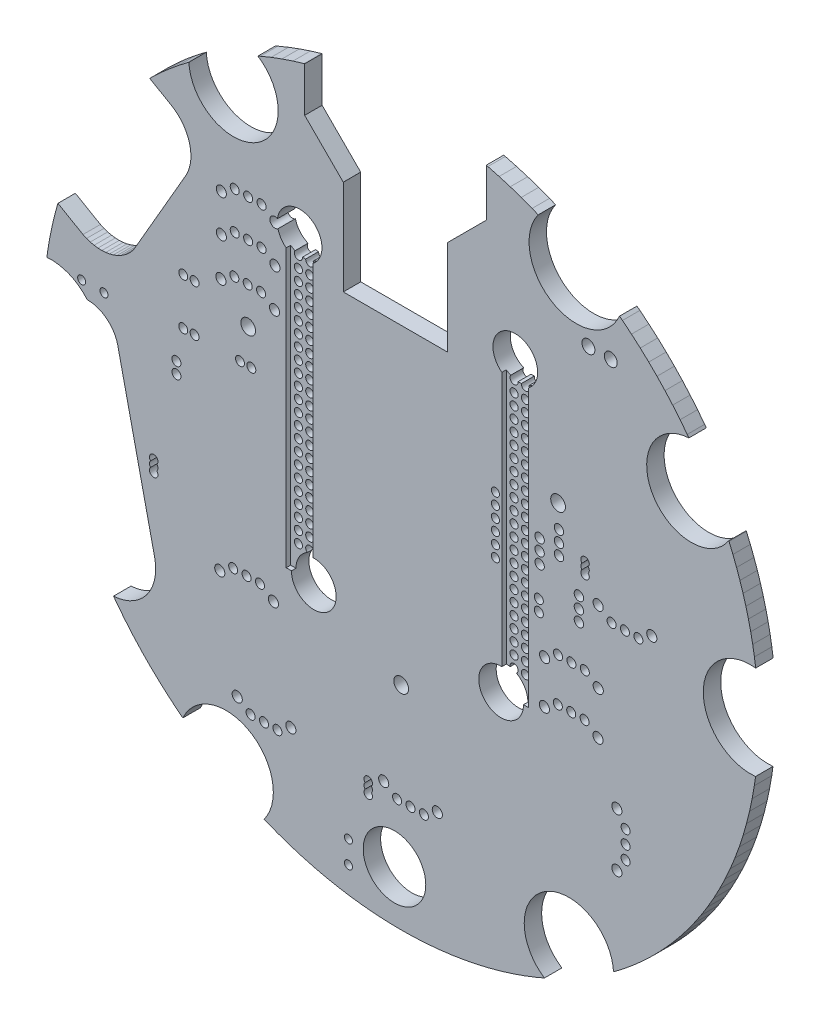
SolidWorks part; units mm, degrees
ref_plane "Płaszczyzna przednia" through (0, 0, 0) normal (0, 0, 1) x (1, 0, 0)
ref_plane "Płaszczyzna górna" through (0, 0, 0) normal (0, 1, 0) x (1, 0, 0)
ref_plane "Płaszczyzna prawa" through (0, 0, 0) normal (1, 0, 0) x (0, 0, -1)
sketch "Szkic1" plane through (0, 0, 0) normal (0, 0, 1) x (1, 0, 0)
  line L362 (-71.5796, -7.9834) -> (-71.3126, -9.14)
  line L363 (-71.3126, -9.14) -> (-68.5352, -8.4988)
  line L364 (-68.5352, -8.4988) -> (-68.1939, -8.42)
  line L365 (-68.1939, -8.42) -> (-67.4966, -8.3528)
  line L366 (-67.4966, -8.3528) -> (-66.7965, -8.3773)
  line L367 (-66.7965, -8.3773) -> (-66.1056, -8.4929)
  line L368 (-66.1056, -8.4929) -> (-65.4357, -8.6977)
  line L369 (-65.4357, -8.6977) -> (-64.7982, -8.9882)
  line L370 (-64.7982, -8.9882) -> (-64.2042, -9.3594)
  line L371 (-64.2042, -9.3594) -> (-63.6636, -9.805)
  line L372 (-63.6636, -9.805) -> (-63.1859, -10.3174)
  line L373 (-63.1859, -10.3174) -> (-62.7791, -10.8877)
  line L374 (-62.7791, -10.8877) -> (-62.4502, -11.5062)
  line L375 (-62.4502, -11.5062) -> (-62.2049, -12.1624)
  line L376 (-62.2049, -12.1624) -> (-62.1261, -12.5037)
  line L377 (-62.1261, -12.5037) -> (-61.3306, -15.949)
  line L378 (-61.3306, -15.949) -> (-61.2518, -16.2903)
  line L379 (-61.2518, -16.2903) -> (-61.1847, -16.9876)
  line L380 (-61.1847, -16.9876) -> (-61.2092, -17.6877)
  line L381 (-61.2092, -17.6877) -> (-61.3248, -18.3787)
  line L382 (-61.3248, -18.3787) -> (-61.5296, -19.0486)
  line L383 (-61.5296, -19.0486) -> (-61.8201, -19.686)
  line L384 (-61.8201, -19.686) -> (-62.1913, -20.2801)
  line L385 (-62.1913, -20.2801) -> (-62.6369, -20.8206)
  line L386 (-62.6369, -20.8206) -> (-63.1492, -21.2984)
  line L387 (-63.1492, -21.2984) -> (-63.7196, -21.7052)
  line L388 (-63.7196, -21.7052) -> (-64.3381, -22.0341)
  line L389 (-64.3381, -22.0341) -> (-64.9942, -22.2794)
  line L390 (-64.9942, -22.2794) -> (-65.3355, -22.3582)
  line L391 (-65.3355, -22.3582) -> (-76.0559, -24.8332)
  line L392 (-76.0559, -24.8332) -> (-75.5463, -26.3728)
  line L393 (-75.5463, -26.3728) -> (-74.6507, -28.8104)
  line L394 (-74.6507, -28.8104) -> (-73.6765, -31.2177)
  line L395 (-73.6765, -31.2177) -> (-73.3045, -32.0573)
  line L396 (-64.3703, -47.5137) -> (-63.5862, -48.5784)
  line L397 (-63.5862, -48.5784) -> (-61.8317, -50.7929)
  line L398 (-61.8317, -50.7929) -> (-60, -52.944)
  line L399 (-60, -52.944) -> (-58.0936, -55.0292)
  line L400 (-58.0936, -55.0292) -> (-56.1147, -57.0457)
  line L401 (-56.1147, -57.0457) -> (-54.0659, -58.9911)
  line L402 (-54.0659, -58.9911) -> (-51.9496, -60.863)
  line L403 (-51.9496, -60.863) -> (-49.7687, -62.659)
  line L404 (-49.7687, -62.659) -> (-48.854, -63.3595)
  line L405 (-30.6643, -73.9045) -> (-30.3309, -74.048)
  line L406 (-30.3309, -74.048) -> (-27.6979, -75.0726)
  line L407 (-27.6979, -75.0726) -> (-25.0304, -76.0036)
  line L408 (-25.0304, -76.0036) -> (-22.3317, -76.8399)
  line L409 (-22.3317, -76.8399) -> (-19.6051, -77.5804)
  line L410 (-19.6051, -77.5804) -> (-16.8541, -78.2241)
  line L411 (-16.8541, -78.2241) -> (-14.0821, -78.7703)
  line L412 (-14.0821, -78.7703) -> (-11.2926, -79.2184)
  line L413 (-11.2926, -79.2184) -> (-8.4889, -79.5676)
  line L414 (-8.4889, -79.5676) -> (-5.6747, -79.8177)
  line L415 (-5.6747, -79.8177) -> (-2.8534, -79.9683)
  line L416 (-2.8534, -79.9683) -> (-0.0286, -80.0192)
  line L417 (-0.0286, -80.0192) -> (2.7963, -79.9703)
  line L418 (2.7963, -79.9703) -> (5.6177, -79.8218)
  line L419 (5.6177, -79.8218) -> (8.4321, -79.5737)
  line L420 (8.4321, -79.5737) -> (11.236, -79.2264)
  line L421 (11.236, -79.2264) -> (14.0259, -78.7804)
  line L422 (14.0259, -78.7804) -> (16.7983, -78.2361)
  line L423 (16.7983, -78.2361) -> (19.5497, -77.5943)
  line L424 (19.5497, -77.5943) -> (22.2768, -76.8558)
  line L425 (22.2768, -76.8558) -> (24.9761, -76.0215)
  line L426 (24.9761, -76.0215) -> (27.6443, -75.0924)
  line L427 (27.6443, -75.0924) -> (30.278, -74.0697)
  line L428 (30.278, -74.0697) -> (32.0581, -73.3051)
  line L429 (47.514, -64.3751) -> (47.9923, -64.0295)
  line L430 (47.9923, -64.0295) -> (50.2037, -62.3107)
  line L431 (50.2037, -62.3107) -> (52.3536, -60.5156)
  line L432 (52.3536, -60.5156) -> (54.4394, -58.6463)
  line L433 (54.4394, -58.6463) -> (56.4584, -56.7052)
  line L434 (56.4584, -56.7052) -> (58.4083, -54.6947)
  line L435 (58.4083, -54.6947) -> (60.2867, -52.6171)
  line L436 (60.2867, -52.6171) -> (62.0911, -50.475)
  line L437 (62.0911, -50.475) -> (63.8195, -48.2711)
  line L438 (63.8195, -48.2711) -> (65.4698, -46.0081)
  line L439 (65.4698, -46.0081) -> (67.0398, -43.6887)
  line L440 (67.0398, -43.6887) -> (68.5277, -41.3158)
  line L441 (68.5277, -41.3158) -> (69.9316, -38.8923)
  line L442 (69.9316, -38.8923) -> (71.2498, -36.4211)
  line L443 (71.2498, -36.4211) -> (72.4808, -33.9053)
  line L444 (72.4808, -33.9053) -> (73.623, -31.348)
  line L445 (73.623, -31.348) -> (74.6749, -28.7523)
  line L446 (74.6749, -28.7523) -> (75.6354, -26.1213)
  line L447 (75.6354, -26.1213) -> (76.5032, -23.4583)
  line L448 (76.5032, -23.4583) -> (77.2773, -20.7666)
  line L449 (77.2773, -20.7666) -> (77.9567, -18.0495)
  line L450 (77.9567, -18.0495) -> (78.5407, -15.3102)
  line L451 (78.5407, -15.3102) -> (79.0284, -12.5522)
  line L452 (79.0284, -12.5522) -> (79.2994, -10.6289)
  line L453 (79.3336, 10.3964) -> (79.0449, 12.4201)
  line L454 (79.0449, 12.4201) -> (78.6613, 14.6547)
  line L455 (78.6613, 14.6547) -> (78.2145, 16.8775)
  line L456 (78.2145, 16.8775) -> (77.7049, 19.0868)
  line L457 (77.7049, 19.0868) -> (77.1329, 21.2808)
  line L458 (77.1329, 21.2808) -> (76.499, 23.4576)
  line L459 (76.499, 23.4576) -> (75.8037, 25.6157)
  line L460 (75.8037, 25.6157) -> (75.0475, 27.7531)
  line L461 (75.0475, 27.7531) -> (74.231, 29.8683)
  line L462 (74.231, 29.8683) -> (73.355, 31.9595)
  line L463 (73.355, 31.9595) -> (73.3082, 32.0629)
  line L464 (64.3736, 47.5139) -> (64.0078, 48.0184)
  line L465 (64.0078, 48.0184) -> (62.4143, 50.0722)
  line L466 (62.4143, 50.0722) -> (60.7549, 52.0732)
  line L467 (60.7549, 52.0732) -> (59.0313, 54.0192)
  line L468 (59.0313, 54.0192) -> (57.2455, 55.9082)
  line L469 (57.2455, 55.9082) -> (55.3992, 57.7382)
  line L470 (55.3992, 57.7382) -> (53.4945, 59.5072)
  line L471 (53.4945, 59.5072) -> (51.5333, 61.2135)
  line L472 (51.5333, 61.2135) -> (49.5177, 62.8551)
  line L473 (49.5177, 62.8551) -> (48.8544, 63.3604)
  line L474 (30.6602, 73.899) -> (29.2981, 74.4606)
  line L475 (29.2981, 74.4606) -> (26.864, 75.373)
  line L476 (26.864, 75.373) -> (24.4015, 76.2059)
  line L477 (24.4015, 76.2059) -> (21.9132, 76.9583)
  line L478 (21.9132, 76.9583) -> (19.4018, 77.6295)
  line L479 (19.4018, 77.6295) -> (19.0436, 77.7128)
  line L480 (19.0436, 77.7128) -> (19.0437, 67.0537)
  line L481 (19.0437, 67.0537) -> (10.4176, 58.4277)
  line L482 (10.4176, 58.4277) -> (10.4176, 37.1511)
  line L483 (10.4176, 37.1511) -> (-12.9504, 37.1511)
  line L484 (-12.9504, 37.1511) -> (-12.9504, 58.4177)
  line L485 (-12.9504, 58.4177) -> (-12.9604, 58.4177)
  line L486 (-12.9604, 58.4177) -> (-21.5964, 67.0537)
  line L487 (-21.5964, 67.0537) -> (-21.5964, 77.0457)
  line L488 (-21.5964, 77.0457) -> (-21.7211, 77.0127)
  line L489 (-21.7211, 77.0127) -> (-24.2112, 76.2665)
  line L490 (-24.2112, 76.2665) -> (-26.6758, 75.4398)
  line L491 (-26.6758, 75.4398) -> (-29.1122, 74.5335)
  line L492 (-29.1122, 74.5335) -> (-31.5179, 73.5485)
  line L493 (-31.5179, 73.5485) -> (-32.0595, 73.306)
  line L494 (-47.5141, 64.3762) -> (-47.8425, 64.1394)
  line L495 (-47.8425, 64.1394) -> (-49.8986, 62.5531)
  line L496 (-49.8986, 62.5531) -> (-51.9022, 60.9009)
  line L497 (-51.9022, 60.9009) -> (-53.8511, 59.1846)
  line L498 (-53.8511, 59.1846) -> (-55.7433, 57.406)
  line L499 (-55.7433, 57.406) -> (-56.2765, 56.8712)
  line L500 (-56.2765, 56.8712) -> (-51.5136, 54.1214)
  line L501 (-51.5136, 54.1214) -> (-51.1354, 53.903)
  line L502 (-51.1354, 53.903) -> (-50.4254, 53.3942)
  line L503 (-50.4254, 53.3942) -> (-49.7687, 52.8183)
  line L504 (-49.7687, 52.8183) -> (-49.1716, 52.1808)
  line L505 (-49.1716, 52.1808) -> (-48.6398, 51.4878)
  line L506 (-48.6398, 51.4878) -> (-48.1786, 50.746)
  line L507 (-48.1786, 50.746) -> (-47.7923, 49.9626)
  line L508 (-47.7923, 49.9626) -> (-47.4846, 49.1452)
  line L509 (-47.4846, 49.1452) -> (-47.2585, 48.3014)
  line L510 (-47.2585, 48.3014) -> (-47.1162, 47.4396)
  line L511 (-47.1162, 47.4396) -> (-47.0591, 46.568)
  line L512 (-47.0591, 46.568) -> (-47.0877, 45.695)
  line L513 (-47.0877, 45.695) -> (-47.2017, 44.829)
  line L514 (-47.2017, 44.829) -> (-47.4, 43.9784)
  line L515 (-47.4, 43.9784) -> (-47.6808, 43.1512)
  line L516 (-47.6808, 43.1512) -> (-48.0413, 42.3556)
  line L517 (-48.0413, 42.3556) -> (-48.2597, 41.9774)
  line L518 (-48.2597, 41.9774) -> (-59.4357, 22.62)
  line L519 (-59.4357, 22.62) -> (-59.654, 22.2418)
  line L520 (-59.654, 22.2418) -> (-60.1628, 21.5318)
  line L521 (-60.1628, 21.5318) -> (-60.7387, 20.8751)
  line L522 (-60.7387, 20.8751) -> (-61.3762, 20.278)
  line L523 (-61.3762, 20.278) -> (-62.0692, 19.7462)
  line L524 (-62.0692, 19.7462) -> (-62.811, 19.285)
  line L525 (-62.811, 19.285) -> (-63.5944, 18.8986)
  line L526 (-63.5944, 18.8986) -> (-64.4119, 18.591)
  line L527 (-64.4119, 18.591) -> (-65.2556, 18.3649)
  line L528 (-65.2556, 18.3649) -> (-66.1174, 18.2226)
  line L529 (-66.1174, 18.2226) -> (-66.989, 18.1655)
  line L530 (-66.989, 18.1655) -> (-67.862, 18.1941)
  line L531 (-67.862, 18.1941) -> (-68.728, 18.3081)
  line L532 (-68.728, 18.3081) -> (-69.5787, 18.5064)
  line L533 (-69.5787, 18.5064) -> (-70.4058, 18.7872)
  line L534 (-70.4058, 18.7872) -> (-71.2014, 19.1477)
  line L535 (-71.2014, 19.1477) -> (-71.5796, 19.366)
  line L536 (-71.5796, 19.366) -> (-76.8174, 22.3901)
  line L537 (-76.8174, 22.3901) -> (-76.8834, 22.1744)
  line L538 (-76.8834, 22.1744) -> (-77.5625, 19.6678)
  line L539 (-77.5625, 19.6678) -> (-78.1599, 17.1405)
  line L540 (-78.1599, 17.1405) -> (-78.6749, 14.5952)
  line L541 (-78.6749, 14.5952) -> (-79.1071, 12.0345)
  line L542 (-79.1071, 12.0345) -> (-79.2897, 10.6872)
  circle A3 centre (0, -32.54) radius 3
  circle A4 centre (35.1087, 20.27) radius 3
  circle A5 centre (-34.2427, 19.77) radius 3
  arc A16 (-71.5796, -7.9834) -> (-79.2897, 10.6872) centre (-78.3301, 0.1563) ccw
  arc A17 (-64.3703, -47.5137) -> (-73.3045, -32.0573) centre (-64.9348, -37.5297) ccw
  arc A18 (-30.6643, -73.9045) -> (-48.854, -63.3595) centre (-39.186, -67.6433) ccw
  arc A19 (47.514, -64.3751) -> (32.0581, -73.3051) centre (37.5297, -64.9348) ccw
  arc A20 (79.3336, 10.3964) -> (79.2994, -10.6289) centre (78.1738, -0.1144) ccw
  arc A21 (64.3736, 47.5139) -> (73.3082, 32.0629) centre (64.9348, 37.5297) ccw
  arc A22 (30.6602, 73.899) -> (48.8544, 63.3604) centre (39.186, 67.6433) ccw
  arc A23 (-47.5141, 64.3762) -> (-32.0595, 73.306) centre (-37.5297, 64.9348) ccw
extrude "Dodanie-wyciągnięcie1" add sketch "Szkic1" along normal blind 3.9
sketch "Sketch1" plane through (0, 0, 3.9) normal (0, 0, 1) x (1, 0, 0)
  line L6 (22.531, 39.311) -> (22.531, -17.7321)
  line L7 (28.531, 39.311) -> (28.531, -22.689)
  line L8 (28.531, -22.689) -> (27.3558, -22.689)
  line L9 (-19.729, 39.311) -> (-19.729, -17.7321)
  line L10 (-25.729, 39.311) -> (-25.729, -22.689)
  line L11 (-25.729, -22.689) -> (-24.5539, -22.6966)
  arc A4 (22.531, -17.7321) -> (27.3558, -22.689) centre (22.356, -22.729) ccw
  arc A5 (-24.5539, -22.6966) -> (-19.729, -17.7321) centre (-19.554, -22.729) ccw
  arc A6 (28.531, 39.311) -> (22.531, 39.311) centre (25.531, 43.311) ccw
  arc A7 (-19.729, 39.311) -> (-25.729, 39.311) centre (-22.729, 43.311) ccw
  point P0 (0, 0)
extrude "Cut-Extrude1" cut sketch "Sketch1" against normal blind 1 contours A7 L10 L11 A5 L9 | A6 L6 A4 L8 L7
sketch "Sketch2" plane through (0, 0, 3.9) normal (0, 0, 1) x (1, 0, 0)
  circle A0 centre (-22.729, 43.311) radius 5
  circle A1 centre (25.531, 43.311) radius 5
  circle A2 centre (22.356, -22.729) radius 5
  circle A3 centre (-19.554, -22.729) radius 5
extrude "Cut-Extrude2" cut sketch "Sketch2" against normal through all
sketch "Sketch3" plane through (0, 0, 3.9) normal (0, 0, 1) x (1, 0, 0)
  line L0 (0, 0) -> (0, -68.54) construction
  line L1 (0, -68.54) -> (-1.5, -68.54) construction
  line L2 (0, 0) -> (-76.8972, 0) construction
  circle A0 centre (0, -32.54) radius 3 construction
  circle A1 centre (-1.5, -68.54) radius 7
  circle A2 centre (-34.2427, 19.77) radius 3 construction
  circle A3 centre (-70.2427, 0) radius 7
  point P7 (-3, -32.54)
  point P8 (72.1497, -57.8392)
  point P10 (3, -32.54)
  dimension "D2" = 14
  dimension "D3" = 4.5
  dimension "D4" = 14
  dimension "D1" = 36
  dimension "D5" = 36
extrude "Cut-Extrude3" cut sketch "Sketch3" against normal through all
sketch "Sketch5" plane through (0, 0, 3.9) normal (0, 0, 1) x (1, 0, 0)
  line L0 (-63.411, 1.5258) -> (-55.1752, -35.35)
  line L181 (-71.5796, -7.9834) -> (-71.3126, -9.14)
  line L182 (-71.3126, -9.14) -> (-68.5352, -8.4988)
  line L183 (-68.5352, -8.4988) -> (-68.1939, -8.42)
  line L184 (-68.1939, -8.42) -> (-67.4966, -8.3528)
  line L185 (-67.4966, -8.3528) -> (-66.7965, -8.3773)
  line L186 (-66.7965, -8.3773) -> (-66.1056, -8.4929)
  line L187 (-66.1056, -8.4929) -> (-65.4357, -8.6977)
  line L188 (-65.4357, -8.6977) -> (-64.7982, -8.9882)
  line L189 (-64.7982, -8.9882) -> (-64.2042, -9.3594)
  line L190 (-64.2042, -9.3594) -> (-63.6636, -9.805)
  line L191 (-63.6636, -9.805) -> (-63.1859, -10.3174)
  line L192 (-63.1859, -10.3174) -> (-62.7791, -10.8877)
  line L193 (-62.7791, -10.8877) -> (-62.4502, -11.5062)
  line L194 (-62.4502, -11.5062) -> (-62.2049, -12.1624)
  line L195 (-62.2049, -12.1624) -> (-62.1261, -12.5037)
  line L196 (-62.1261, -12.5037) -> (-61.3306, -15.949)
  line L197 (-61.3306, -15.949) -> (-61.2518, -16.2903)
  line L198 (-61.2518, -16.2903) -> (-61.1847, -16.9876)
  line L199 (-61.1847, -16.9876) -> (-61.2092, -17.6877)
  line L200 (-61.2092, -17.6877) -> (-61.3248, -18.3787)
  line L201 (-61.3248, -18.3787) -> (-61.5296, -19.0486)
  line L202 (-61.5296, -19.0486) -> (-61.8201, -19.686)
  line L203 (-61.8201, -19.686) -> (-62.1913, -20.2801)
  line L204 (-62.1913, -20.2801) -> (-62.6369, -20.8206)
  line L205 (-62.6369, -20.8206) -> (-63.1492, -21.2984)
  line L206 (-63.1492, -21.2984) -> (-63.7196, -21.7052)
  line L207 (-63.7196, -21.7052) -> (-64.3381, -22.0341)
  line L208 (-64.3381, -22.0341) -> (-64.9942, -22.2794)
  line L209 (-64.9942, -22.2794) -> (-65.3355, -22.3582)
  line L210 (-65.3355, -22.3582) -> (-76.0559, -24.8332)
  line L211 (-76.0559, -24.8332) -> (-75.5463, -26.3728)
  line L212 (-75.5463, -26.3728) -> (-74.6507, -28.8104)
  line L213 (-74.6507, -28.8104) -> (-73.6765, -31.2177)
  line L214 (-73.6765, -31.2177) -> (-73.3045, -32.0573)
  line L215 (-64.3703, -47.5137) -> (-63.5862, -48.5784)
  line L216 (-63.5862, -48.5784) -> (-61.8317, -50.7929)
  line L217 (-61.8317, -50.7929) -> (-60, -52.944)
  line L218 (-60, -52.944) -> (-58.0936, -55.0292)
  line L219 (-58.0936, -55.0292) -> (-56.1147, -57.0457)
  line L220 (-56.1147, -57.0457) -> (-54.0659, -58.9911)
  line L221 (-54.0659, -58.9911) -> (-51.9496, -60.863)
  line L222 (-51.9496, -60.863) -> (-49.7687, -62.659)
  line L223 (-49.7687, -62.659) -> (-48.854, -63.3595)
  line L224 (-30.6643, -73.9045) -> (-30.3309, -74.048)
  line L225 (-30.3309, -74.048) -> (-27.6979, -75.0726)
  line L226 (-27.6979, -75.0726) -> (-25.0304, -76.0036)
  line L227 (-25.0304, -76.0036) -> (-22.3317, -76.8399)
  line L228 (-22.3317, -76.8399) -> (-19.6051, -77.5804)
  line L229 (-19.6051, -77.5804) -> (-16.8541, -78.2241)
  line L230 (-16.8541, -78.2241) -> (-14.0821, -78.7703)
  line L231 (-14.0821, -78.7703) -> (-11.2926, -79.2184)
  line L232 (-11.2926, -79.2184) -> (-8.4889, -79.5676)
  line L233 (-8.4889, -79.5676) -> (-5.6747, -79.8177)
  line L234 (-5.6747, -79.8177) -> (-2.8534, -79.9683)
  line L235 (-2.8534, -79.9683) -> (-0.0286, -80.0192)
  line L236 (-0.0286, -80.0192) -> (2.7963, -79.9703)
  line L237 (2.7963, -79.9703) -> (5.6177, -79.8218)
  line L238 (5.6177, -79.8218) -> (8.4321, -79.5737)
  line L239 (8.4321, -79.5737) -> (11.236, -79.2264)
  line L240 (11.236, -79.2264) -> (14.0259, -78.7804)
  line L241 (14.0259, -78.7804) -> (16.7983, -78.2361)
  line L242 (16.7983, -78.2361) -> (19.5497, -77.5943)
  line L243 (19.5497, -77.5943) -> (22.2768, -76.8558)
  line L244 (22.2768, -76.8558) -> (24.9761, -76.0215)
  line L245 (24.9761, -76.0215) -> (27.6443, -75.0924)
  line L246 (27.6443, -75.0924) -> (30.278, -74.0697)
  line L247 (30.278, -74.0697) -> (32.0581, -73.3051)
  line L248 (47.514, -64.3751) -> (47.9923, -64.0295)
  line L249 (47.9923, -64.0295) -> (50.2037, -62.3107)
  line L250 (50.2037, -62.3107) -> (52.3536, -60.5156)
  line L251 (52.3536, -60.5156) -> (54.4394, -58.6463)
  line L252 (54.4394, -58.6463) -> (56.4584, -56.7052)
  line L253 (56.4584, -56.7052) -> (58.4083, -54.6947)
  line L254 (58.4083, -54.6947) -> (60.2867, -52.6171)
  line L255 (60.2867, -52.6171) -> (62.0911, -50.475)
  line L256 (62.0911, -50.475) -> (63.8195, -48.2711)
  line L257 (63.8195, -48.2711) -> (65.4698, -46.0081)
  line L258 (65.4698, -46.0081) -> (67.0398, -43.6887)
  line L259 (67.0398, -43.6887) -> (68.5277, -41.3158)
  line L260 (68.5277, -41.3158) -> (69.9316, -38.8923)
  line L261 (69.9316, -38.8923) -> (71.2498, -36.4211)
  line L262 (71.2498, -36.4211) -> (72.4808, -33.9053)
  line L263 (72.4808, -33.9053) -> (73.623, -31.348)
  line L264 (73.623, -31.348) -> (74.6749, -28.7523)
  line L265 (74.6749, -28.7523) -> (75.6354, -26.1213)
  line L266 (75.6354, -26.1213) -> (76.5032, -23.4583)
  line L267 (76.5032, -23.4583) -> (77.2773, -20.7666)
  line L268 (77.2773, -20.7666) -> (77.9567, -18.0495)
  line L269 (77.9567, -18.0495) -> (78.5407, -15.3102)
  line L270 (78.5407, -15.3102) -> (79.0284, -12.5522)
  line L271 (79.0284, -12.5522) -> (79.2994, -10.6289)
  line L272 (79.3336, 10.3964) -> (79.0449, 12.4201)
  line L273 (79.0449, 12.4201) -> (78.6613, 14.6547)
  line L274 (78.6613, 14.6547) -> (78.2145, 16.8775)
  line L275 (78.2145, 16.8775) -> (77.7049, 19.0868)
  line L276 (77.7049, 19.0868) -> (77.1329, 21.2808)
  line L277 (77.1329, 21.2808) -> (76.499, 23.4576)
  line L278 (76.499, 23.4576) -> (75.8037, 25.6157)
  line L279 (75.8037, 25.6157) -> (75.0475, 27.7531)
  line L280 (75.0475, 27.7531) -> (74.231, 29.8683)
  line L281 (74.231, 29.8683) -> (73.355, 31.9595)
  line L282 (73.355, 31.9595) -> (73.3082, 32.0629)
  line L283 (64.3736, 47.5139) -> (64.0078, 48.0184)
  line L284 (64.0078, 48.0184) -> (62.4143, 50.0722)
  line L285 (62.4143, 50.0722) -> (60.7549, 52.0732)
  line L286 (60.7549, 52.0732) -> (59.0313, 54.0192)
  line L287 (59.0313, 54.0192) -> (57.2455, 55.9082)
  line L288 (57.2455, 55.9082) -> (55.3992, 57.7382)
  line L289 (55.3992, 57.7382) -> (53.4945, 59.5072)
  line L290 (53.4945, 59.5072) -> (51.5333, 61.2135)
  line L291 (51.5333, 61.2135) -> (49.5177, 62.8551)
  line L292 (49.5177, 62.8551) -> (48.8544, 63.3604)
  line L293 (30.6602, 73.899) -> (29.2981, 74.4606)
  line L294 (29.2981, 74.4606) -> (26.864, 75.373)
  line L295 (26.864, 75.373) -> (24.4015, 76.2059)
  line L296 (24.4015, 76.2059) -> (21.9132, 76.9583)
  line L297 (21.9132, 76.9583) -> (19.4018, 77.6295)
  line L298 (19.4018, 77.6295) -> (19.0436, 77.7128)
  line L299 (19.0436, 77.7128) -> (19.0437, 67.0537)
  line L300 (19.0437, 67.0537) -> (10.4176, 58.4277)
  line L301 (10.4176, 58.4277) -> (10.4176, 37.1511)
  line L302 (10.4176, 37.1511) -> (-12.9504, 37.1511)
  line L303 (-12.9504, 37.1511) -> (-12.9504, 58.4177)
  line L304 (-12.9504, 58.4177) -> (-12.9604, 58.4177)
  line L305 (-12.9604, 58.4177) -> (-21.5964, 67.0537)
  line L306 (-21.5964, 67.0537) -> (-21.5964, 77.0457)
  line L307 (-21.5964, 77.0457) -> (-21.7211, 77.0127)
  line L308 (-21.7211, 77.0127) -> (-24.2112, 76.2665)
  line L309 (-24.2112, 76.2665) -> (-26.6758, 75.4398)
  line L310 (-26.6758, 75.4398) -> (-29.1122, 74.5335)
  line L311 (-29.1122, 74.5335) -> (-31.5179, 73.5485)
  line L312 (-31.5179, 73.5485) -> (-32.0595, 73.306)
  line L313 (-47.5141, 64.3762) -> (-47.8425, 64.1394)
  line L314 (-47.8425, 64.1394) -> (-49.8986, 62.5531)
  line L315 (-49.8986, 62.5531) -> (-51.9022, 60.9009)
  line L316 (-51.9022, 60.9009) -> (-53.8511, 59.1846)
  line L317 (-53.8511, 59.1846) -> (-55.7433, 57.406)
  line L318 (-55.7433, 57.406) -> (-56.2765, 56.8712)
  line L319 (-56.2765, 56.8712) -> (-51.5136, 54.1214)
  line L320 (-51.5136, 54.1214) -> (-51.1354, 53.903)
  line L321 (-51.1354, 53.903) -> (-50.4254, 53.3942)
  line L322 (-50.4254, 53.3942) -> (-49.7687, 52.8183)
  line L323 (-49.7687, 52.8183) -> (-49.1716, 52.1808)
  line L324 (-49.1716, 52.1808) -> (-48.6398, 51.4878)
  line L325 (-48.6398, 51.4878) -> (-48.1786, 50.746)
  line L326 (-48.1786, 50.746) -> (-47.7923, 49.9626)
  line L327 (-47.7923, 49.9626) -> (-47.4846, 49.1452)
  line L328 (-47.4846, 49.1452) -> (-47.2585, 48.3014)
  line L329 (-47.2585, 48.3014) -> (-47.1162, 47.4396)
  line L330 (-47.1162, 47.4396) -> (-47.0591, 46.568)
  line L331 (-47.0591, 46.568) -> (-47.0877, 45.695)
  line L332 (-47.0877, 45.695) -> (-47.2017, 44.829)
  line L333 (-47.2017, 44.829) -> (-47.4, 43.9784)
  line L334 (-47.4, 43.9784) -> (-47.6808, 43.1512)
  line L335 (-47.6808, 43.1512) -> (-48.0413, 42.3556)
  line L336 (-48.0413, 42.3556) -> (-48.2597, 41.9774)
  line L337 (-48.2597, 41.9774) -> (-59.4357, 22.62)
  line L338 (-59.4357, 22.62) -> (-59.654, 22.2418)
  line L339 (-59.654, 22.2418) -> (-60.1628, 21.5318)
  line L340 (-60.1628, 21.5318) -> (-60.7387, 20.8751)
  line L341 (-60.7387, 20.8751) -> (-61.3762, 20.278)
  line L342 (-61.3762, 20.278) -> (-62.0692, 19.7462)
  line L343 (-62.0692, 19.7462) -> (-62.811, 19.285)
  line L344 (-62.811, 19.285) -> (-63.5944, 18.8986)
  line L345 (-63.5944, 18.8986) -> (-64.4119, 18.591)
  line L346 (-64.4119, 18.591) -> (-65.2556, 18.3649)
  line L347 (-65.2556, 18.3649) -> (-66.1174, 18.2226)
  line L348 (-66.1174, 18.2226) -> (-66.989, 18.1655)
  line L349 (-66.989, 18.1655) -> (-67.862, 18.1941)
  line L350 (-67.862, 18.1941) -> (-68.728, 18.3081)
  line L351 (-68.728, 18.3081) -> (-69.5787, 18.5064)
  line L352 (-69.5787, 18.5064) -> (-70.4058, 18.7872)
  line L353 (-70.4058, 18.7872) -> (-71.2014, 19.1477)
  line L354 (-71.2014, 19.1477) -> (-71.5796, 19.366)
  line L355 (-71.5796, 19.366) -> (-76.8174, 22.3901)
  line L356 (-76.8174, 22.3901) -> (-76.8834, 22.1744)
  line L357 (-76.8834, 22.1744) -> (-77.5625, 19.6678)
  line L358 (-77.5625, 19.6678) -> (-78.1599, 17.1405)
  line L359 (-78.1599, 17.1405) -> (-78.6749, 14.5952)
  line L360 (-78.6749, 14.5952) -> (-79.1071, 12.0345)
  line L361 (-79.1071, 12.0345) -> (-79.2897, 10.6872)
  line L362 (-71.5796, -7.9834) -> (-71.3126, -9.14)
  line L363 (-71.3126, -9.14) -> (-68.5352, -8.4988)
  line L364 (-68.5352, -8.4988) -> (-68.1939, -8.42)
  line L365 (-68.1939, -8.42) -> (-67.4966, -8.3528)
  line L366 (-67.4966, -8.3528) -> (-66.7965, -8.3773)
  line L367 (-66.7965, -8.3773) -> (-66.1056, -8.4929)
  line L368 (-66.1056, -8.4929) -> (-65.4357, -8.6977)
  line L369 (-65.4357, -8.6977) -> (-64.7982, -8.9882)
  line L370 (-64.7982, -8.9882) -> (-64.2042, -9.3594)
  line L371 (-64.2042, -9.3594) -> (-63.6636, -9.805)
  line L372 (-63.6636, -9.805) -> (-63.1859, -10.3174)
  line L373 (-63.1859, -10.3174) -> (-62.7791, -10.8877)
  line L374 (-62.7791, -10.8877) -> (-62.4502, -11.5062)
  line L375 (-62.4502, -11.5062) -> (-62.2049, -12.1624)
  line L376 (-62.2049, -12.1624) -> (-62.1261, -12.5037)
  line L377 (-62.1261, -12.5037) -> (-61.3306, -15.949)
  line L378 (-61.3306, -15.949) -> (-61.2518, -16.2903)
  line L379 (-61.2518, -16.2903) -> (-61.1847, -16.9876)
  line L380 (-61.1847, -16.9876) -> (-61.2092, -17.6877)
  line L381 (-61.2092, -17.6877) -> (-61.3248, -18.3787)
  line L382 (-61.3248, -18.3787) -> (-61.5296, -19.0486)
  line L383 (-61.5296, -19.0486) -> (-61.8201, -19.686)
  line L384 (-61.8201, -19.686) -> (-62.1913, -20.2801)
  line L385 (-62.1913, -20.2801) -> (-62.6369, -20.8206)
  line L386 (-62.6369, -20.8206) -> (-63.1492, -21.2984)
  line L387 (-63.1492, -21.2984) -> (-63.7196, -21.7052)
  line L388 (-63.7196, -21.7052) -> (-64.3381, -22.0341)
  line L389 (-64.3381, -22.0341) -> (-64.9942, -22.2794)
  line L390 (-64.9942, -22.2794) -> (-65.3355, -22.3582)
  line L391 (-65.3355, -22.3582) -> (-76.0559, -24.8332)
  line L392 (-76.0559, -24.8332) -> (-75.5463, -26.3728)
  line L393 (-75.5463, -26.3728) -> (-74.6507, -28.8104)
  line L394 (-74.6507, -28.8104) -> (-73.6765, -31.2177)
  line L395 (-73.6765, -31.2177) -> (-73.3045, -32.0573)
  arc A10 (-70.5391, -6.9937) -> (-70.2687, 7) centre (-70.2427, 0) ccw
  arc A11 (-71.5796, -7.9834) -> (-70.5391, -6.9937) centre (-78.3301, 0.1563) ccw
  arc A12 (-64.3703, -47.5137) -> (-73.3045, -32.0573) centre (-64.9348, -37.5297) ccw
  arc A13 (-30.6643, -73.9045) -> (-48.854, -63.3595) centre (-39.186, -67.6433) ccw
  arc A14 (47.514, -64.3751) -> (32.0581, -73.3051) centre (37.5297, -64.9348) ccw
  arc A15 (79.3336, 10.3964) -> (79.2994, -10.6289) centre (78.1738, -0.1144) ccw
  arc A16 (64.3736, 47.5139) -> (73.3082, 32.0629) centre (64.9348, 37.5297) ccw
  arc A17 (30.6602, 73.899) -> (48.8544, 63.3604) centre (39.186, 67.6433) ccw
  arc A18 (-47.5141, 64.3762) -> (-32.0595, 73.306) centre (-37.5297, 64.9348) ccw
  arc A19 (-70.2687, 7) -> (-79.2897, 10.6872) centre (-78.3301, 0.1563) ccw
  arc A20 (-70.5391, -6.9937) -> (-63.411, 1.5258) centre (-70.2427, 0) ccw
  arc A21 (-71.5796, -7.9834) -> (-70.5391, -6.9937) centre (-78.3301, 0.1563) ccw
  arc A22 (-55.1752, -35.35) -> (-73.3045, -32.0573) centre (-64.9348, -37.5297) ccw
  dimension "D1" = 0
extrude "Cut-Extrude4" cut sketch "Sketch5" against normal blind 20
sketch "Sketch6" plane through (0, 0, 0) normal (0, 0, -1) x (-1, 0, 0)
  circle A0 centre (31.2484, 36.5741) radius 1.01
  circle A1 centre (48.7744, 22.6041) radius 1
  circle A2 centre (31.2484, 36.5741) radius 0.51 construction
  circle A3 centre (46.2344, 22.6041) radius 1
  circle A4 centre (48.7744, 22.6041) radius 0.5 construction
  circle A5 centre (40.2484, 42.9961) radius 1.135
  circle A6 centre (46.2344, 22.6041) radius 0.5 construction
  circle A7 centre (37.2484, 44.9561) radius 1.01
  circle A8 centre (40.2484, 42.9961) radius 0.635 construction
  circle A9 centre (34.2484, 44.9561) radius 1.01
  circle A10 centre (37.2484, 44.9561) radius 0.51 construction
  circle A11 centre (31.2484, 44.9561) radius 1.01
  circle A12 centre (34.2484, 44.9561) radius 0.51 construction
  circle A13 centre (28.2484, 42.9961) radius 1.135
  circle A14 centre (31.2484, 44.9561) radius 0.51 construction
  circle A15 centre (37.2484, 36.5741) radius 1.01
  circle A16 centre (28.2484, 42.9961) radius 0.635 construction
  circle A17 centre (34.2484, 36.5741) radius 1.01
  circle A19 centre (40.2484, 34.6141) radius 1.135
  circle A20 centre (37.2484, 36.5741) radius 0.51 construction
  circle A21 centre (55.3784, -17.7819) radius 0.95
  circle A22 centre (34.2484, 36.5741) radius 0.51 construction
  circle A23 centre (55.3784, -19.0519) radius 0.95
  circle A24 centre (40.2484, 34.6141) radius 0.635 construction
  circle A25 centre (23.9994, -10.0289) radius 0.91
  circle A26 centre (55.3784, -17.7819) radius 0.45 construction
  circle A27 centre (23.9994, -12.5689) radius 0.91
  circle A28 centre (55.3784, -19.0519) radius 0.45 construction
  circle A29 centre (21.4594, -10.0289) radius 0.91
  circle A30 centre (23.9994, -10.0289) radius 0.41 construction
  circle A31 centre (21.4594, -12.5689) radius 0.91
  circle A32 centre (23.9994, -12.5689) radius 0.41 construction
  circle A33 centre (23.9994, -15.1089) radius 0.91
  circle A34 centre (21.4594, -10.0289) radius 0.41 construction
  circle A35 centre (23.9994, -17.6489) radius 0.91
  circle A36 centre (21.4594, -12.5689) radius 0.41 construction
  circle A37 centre (21.4594, -15.1089) radius 0.91
  circle A38 centre (23.9994, -15.1089) radius 0.41 construction
  circle A39 centre (21.4594, -17.6489) radius 0.91
  circle A40 centre (23.9994, -17.6489) radius 0.41 construction
  circle A41 centre (37.5984, -28.7039) radius 1.01
  circle A42 centre (21.4594, -15.1089) radius 0.41 construction
  circle A43 centre (34.5984, -28.7039) radius 1.01
  circle A44 centre (21.4594, -17.6489) radius 0.41 construction
  circle A45 centre (40.5984, -30.6639) radius 1.135
  circle A47 centre (31.5984, -28.7039) radius 1.01
  circle A48 centre (37.5984, -28.7039) radius 0.51 construction
  circle A49 centre (28.5984, -30.6639) radius 1.135
  circle A50 centre (34.5984, -28.7039) radius 0.51 construction
  circle A51 centre (36.6924, -53.1599) radius 1.135
  circle A52 centre (40.5984, -30.6639) radius 0.635 construction
  circle A53 centre (33.6924, -55.1199) radius 1.01
  circle A54 centre (31.5984, -28.7039) radius 0.51 construction
  circle A55 centre (30.6924, -55.1199) radius 1.01
  circle A56 centre (28.5984, -30.6639) radius 0.635 construction
  circle A57 centre (27.6924, -55.1199) radius 1.01
  circle A58 centre (36.6924, -53.1599) radius 0.635 construction
  circle A59 centre (24.6924, -53.1599) radius 1.135
  circle A60 centre (33.6924, -55.1199) radius 0.51 construction
  circle A61 centre (11.8004, -68.2999) radius 0.9
  circle A62 centre (30.6924, -55.1199) radius 0.51 construction
  circle A63 centre (11.8004, -73.2999) radius 0.9
  circle A64 centre (27.6924, -55.1199) radius 0.51 construction
  circle A65 centre (-24.2606, -10.0289) radius 0.91
  circle A66 centre (24.6924, -53.1599) radius 0.635 construction
  circle A67 centre (-26.8006, -10.0289) radius 0.91
  circle A68 centre (11.8004, -68.2999) radius 0.4 construction
  circle A69 centre (-24.2606, -12.5689) radius 0.91
  circle A70 centre (11.8004, -73.2999) radius 0.4 construction
  circle A71 centre (-26.8006, -12.5689) radius 0.91
  circle A73 centre (-24.2606, -15.1089) radius 0.91
  circle A75 centre (-26.8006, -15.1089) radius 0.91
  circle A76 centre (-24.2606, -10.0289) radius 0.41 construction
  circle A77 centre (-24.2606, -17.6489) radius 0.91
  circle A78 centre (-26.8006, -10.0289) radius 0.41 construction
  circle A79 centre (-26.8006, -17.6489) radius 0.91
  circle A80 centre (-24.2606, -12.5689) radius 0.41 construction
  circle A81 centre (-32.0936, -11.1059) radius 1.135
  circle A82 centre (-26.8006, -12.5689) radius 0.41 construction
  circle A83 centre (-35.0456, -18.7979) radius 1.01
  circle A84 centre (-24.2606, -15.1089) radius 0.41 construction
  circle A85 centre (-32.0456, -20.7579) radius 1.135
  circle A86 centre (-26.8006, -15.1089) radius 0.41 construction
  circle A87 centre (-38.0456, -18.7979) radius 1.01
  circle A88 centre (-24.2606, -17.6489) radius 0.41 construction
  circle A89 centre (-44.0936, -11.1059) radius 1.135
  circle A90 centre (-26.8006, -17.6489) radius 0.41 construction
  circle A91 centre (-41.0456, -18.7979) radius 1.01
  circle A92 centre (-32.0936, -11.1059) radius 0.635 construction
  circle A93 centre (-44.0456, -20.7579) radius 1.135
  circle A94 centre (-35.0456, -18.7979) radius 0.51 construction
  circle A95 centre (-48.2646, -32.3559) radius 1.135
  circle A96 centre (-32.0456, -20.7579) radius 0.635 construction
  circle A97 centre (-50.2246, -35.3559) radius 1.01
  circle A98 centre (-38.0456, -18.7979) radius 0.51 construction
  circle A99 centre (-50.2246, -38.3559) radius 1.01
  circle A100 centre (-44.0936, -11.1059) radius 0.635 construction
  circle A101 centre (-50.2246, -41.3559) radius 1.01
  circle A102 centre (-41.0456, -18.7979) radius 0.51 construction
  circle A103 centre (3.9164, -53.1539) radius 1.135
  circle A104 centre (-44.0456, -20.7579) radius 0.635 construction
  arc A105 (8.0789, -55.5009) -> (6.6658, -55.5009) centre (7.3724, -54.8659) ccw
  circle A106 centre (-48.2646, -32.3559) radius 0.635 construction
  arc A107 (6.6658, -55.5009) -> (6.6658, -56.7709) centre (7.3724, -56.1359) ccw
  circle A108 centre (-50.2246, -35.3559) radius 0.51 construction
  arc A109 (6.6658, -56.7709) -> (8.0789, -56.7709) centre (7.3724, -57.4059) ccw
  circle A110 centre (-50.2246, -38.3559) radius 0.51 construction
  circle A111 centre (0.9164, -55.1139) radius 1.01
  circle A112 centre (-50.2246, -41.3559) radius 0.51 construction
  circle A113 centre (-2.0836, -55.1139) radius 1.01
  circle A114 centre (3.9164, -53.1539) radius 0.635 construction
  circle A115 centre (-5.0836, -55.1139) radius 1.01
  arc A116 (7.6431, -55.2253) -> (7.1016, -55.2253) centre (7.3724, -54.8659) ccw construction
  circle A117 centre (-8.0836, -53.1539) radius 1.135
  arc A118 (7.1016, -55.7764) -> (7.1016, -56.4953) centre (7.3724, -56.1359) ccw construction
  circle A119 centre (-48.2646, -44.3559) radius 1.135
  arc A120 (7.1016, -57.0464) -> (7.6431, -57.0464) centre (7.3724, -57.4059) ccw construction
  arc A121 (-41.8482, 10.0311) -> (-40.4351, 10.0311) centre (-41.1416, 9.3961) ccw
  circle A122 centre (0.9164, -55.1139) radius 0.51 construction
  circle A123 centre (-24.2606, 5.2111) radius 0.91
  circle A124 centre (-2.0836, -55.1139) radius 0.51 construction
  circle A125 centre (-26.8006, 5.2111) radius 0.91
  circle A126 centre (-5.0836, -55.1139) radius 0.51 construction
  circle A127 centre (-24.2606, 2.6711) radius 0.91
  circle A128 centre (-8.0836, -53.1539) radius 0.635 construction
  circle A129 centre (-26.8006, 2.6711) radius 0.91
  circle A131 centre (-24.2606, 0.1311) radius 0.91
  circle A133 centre (-26.8006, 0.1311) radius 0.91
  circle A134 centre (-48.2646, -44.3559) radius 0.635 construction
  circle A135 centre (-30.7996, -0.4599) radius 1.01
  circle A137 centre (-39.7676, 4.6331) radius 1.05
  circle A138 centre (-24.2606, 5.2111) radius 0.41 construction
  circle A139 centre (-39.7676, 2.0931) radius 1.05
  circle A140 centre (-26.8006, 5.2111) radius 0.41 construction
  circle A141 centre (-39.7676, -0.4469) radius 1.05
  circle A142 centre (-24.2606, 2.6711) radius 0.41 construction
  circle A143 centre (-24.2606, -2.4089) radius 0.91
  circle A144 centre (-26.8006, 2.6711) radius 0.41 construction
  circle A145 centre (-26.8006, -2.4089) radius 0.91
  circle A146 centre (-24.2606, 0.1311) radius 0.41 construction
  circle A147 centre (-24.2606, -4.9489) radius 0.91
  circle A148 centre (-26.8006, 0.1311) radius 0.41 construction
  circle A149 centre (-26.8006, -4.9489) radius 0.91
  circle A150 centre (-30.7996, -0.4599) radius 0.51 construction
  circle A151 centre (-30.7996, -2.9999) radius 1.01
  circle A152 centre (-39.7676, 4.6331) radius 0.55 construction
  circle A153 centre (-24.2606, -7.4889) radius 0.91
  circle A154 centre (-39.7676, 2.0931) radius 0.55 construction
  circle A155 centre (-26.8006, -7.4889) radius 0.91
  circle A156 centre (-39.7676, -0.4469) radius 0.55 construction
  circle A157 centre (-35.0936, -9.1459) radius 1.01
  circle A158 centre (-24.2606, -2.4089) radius 0.41 construction
  circle A159 centre (-38.0936, -9.1459) radius 1.01
  circle A160 centre (-26.8006, -2.4089) radius 0.41 construction
  circle A161 centre (-44.0796, 5.0061) radius 1.135
  circle A162 centre (-24.2606, -4.9489) radius 0.41 construction
  circle A163 centre (-47.0796, 3.0461) radius 1.01
  circle A164 centre (-26.8006, -4.9489) radius 0.41 construction
  circle A165 centre (-50.0796, 3.0461) radius 1.01
  circle A166 centre (-30.7996, -2.9999) radius 0.51 construction
  circle A167 centre (-56.0796, 5.0061) radius 1.135
  circle A168 centre (-24.2606, -7.4889) radius 0.41 construction
  circle A169 centre (-53.0796, 3.0461) radius 1.01
  circle A170 centre (-26.8006, -7.4889) radius 0.41 construction
  circle A171 centre (-41.0936, -9.1459) radius 1.01
  circle A172 centre (-35.0936, -9.1459) radius 0.51 construction
  circle A173 centre (55.3784, -16.5119) radius 0.95
  circle A174 centre (-38.0936, -9.1459) radius 0.51 construction
  arc A175 (-41.8482, 11.3011) -> (-41.8482, 10.0311) centre (-41.1416, 10.6661) ccw
  circle A176 centre (-44.0796, 5.0061) radius 0.635 construction
  circle A177 centre (21.4594, 10.2911) radius 0.91
  circle A178 centre (-47.0796, 3.0461) radius 0.51 construction
  circle A179 centre (21.4594, 7.7511) radius 0.91
  circle A180 centre (-50.0796, 3.0461) radius 0.51 construction
  circle A181 centre (23.9994, 5.2111) radius 0.91
  circle A182 centre (-56.0796, 5.0061) radius 0.635 construction
  circle A183 centre (23.9994, 2.6711) radius 0.91
  circle A184 centre (-53.0796, 3.0461) radius 0.51 construction
  circle A185 centre (21.4594, 5.2111) radius 0.91
  circle A186 centre (-41.0936, -9.1459) radius 0.51 construction
  circle A187 centre (21.4594, 2.6711) radius 0.91
  circle A188 centre (55.3784, -16.5119) radius 0.45 construction
  circle A189 centre (23.9994, 0.1311) radius 0.91
  circle A191 centre (21.4594, 0.1311) radius 0.91
  circle A192 centre (21.4594, 10.2911) radius 0.41 construction
  circle A193 centre (23.9994, -2.4089) radius 0.91
  circle A194 centre (21.4594, 7.7511) radius 0.41 construction
  circle A195 centre (23.9994, -4.9489) radius 0.91
  circle A196 centre (23.9994, 5.2111) radius 0.41 construction
  circle A197 centre (21.4594, -2.4089) radius 0.91
  circle A198 centre (23.9994, 2.6711) radius 0.41 construction
  circle A199 centre (21.4594, -4.9489) radius 0.91
  circle A200 centre (21.4594, 5.2111) radius 0.41 construction
  circle A201 centre (23.9994, -7.4889) radius 0.91
  circle A202 centre (21.4594, 2.6711) radius 0.41 construction
  circle A203 centre (21.4594, -7.4889) radius 0.91
  circle A204 centre (23.9994, 0.1311) radius 0.41 construction
  circle A205 centre (-41.8996, 54.0001) radius 1.45
  circle A206 centre (21.4594, 0.1311) radius 0.41 construction
  circle A207 centre (-46.8996, 54.0001) radius 1.45
  circle A208 centre (23.9994, -2.4089) radius 0.41 construction
  circle A209 centre (-24.2606, 38.2311) radius 0.91
  circle A210 centre (23.9994, -4.9489) radius 0.41 construction
  circle A211 centre (-26.8006, 38.2311) radius 0.91
  circle A212 centre (21.4594, -2.4089) radius 0.41 construction
  circle A213 centre (-24.2606, 35.6911) radius 0.91
  circle A214 centre (21.4594, -4.9489) radius 0.41 construction
  circle A215 centre (-26.8006, 35.6911) radius 0.91
  circle A216 centre (23.9994, -7.4889) radius 0.41 construction
  circle A217 centre (-24.2606, 33.1511) radius 0.91
  circle A218 centre (21.4594, -7.4889) radius 0.41 construction
  circle A219 centre (-26.8006, 33.1511) radius 0.91
  circle A221 centre (-24.2606, 30.6111) radius 0.91
  circle A222 centre (-41.8996, 54.0001) radius 0.95 construction
  circle A223 centre (-26.8006, 30.6111) radius 0.91
  circle A224 centre (-46.8996, 54.0001) radius 0.95 construction
  circle A225 centre (-24.2606, 28.0711) radius 0.91
  circle A226 centre (-24.2606, 38.2311) radius 0.41 construction
  circle A227 centre (-26.8006, 28.0711) radius 0.91
  circle A228 centre (-26.8006, 38.2311) radius 0.41 construction
  circle A229 centre (-24.2606, 25.5311) radius 0.91
  circle A230 centre (-24.2606, 35.6911) radius 0.41 construction
  circle A231 centre (-26.8006, 25.5311) radius 0.91
  circle A232 centre (-26.8006, 35.6911) radius 0.41 construction
  circle A233 centre (-24.2606, 22.9911) radius 0.91
  circle A234 centre (-24.2606, 33.1511) radius 0.41 construction
  circle A235 centre (-26.8006, 22.9911) radius 0.91
  circle A236 centre (-26.8006, 33.1511) radius 0.41 construction
  circle A238 centre (-24.2606, 30.6111) radius 0.41 construction
  circle A240 centre (-26.8006, 30.6111) radius 0.41 construction
  circle A241 centre (-21.0856, 15.3711) radius 0.91
  circle A242 centre (-24.2606, 28.0711) radius 0.41 construction
  circle A243 centre (-21.0856, 12.8311) radius 0.91
  circle A244 centre (-26.8006, 28.0711) radius 0.41 construction
  circle A245 centre (-21.0856, 10.2911) radius 0.91
  circle A246 centre (-24.2606, 25.5311) radius 0.41 construction
  circle A247 centre (-21.0856, 7.7511) radius 0.91
  circle A248 centre (-26.8006, 25.5311) radius 0.41 construction
  circle A249 centre (-21.0856, 5.2111) radius 0.91
  circle A250 centre (-24.2606, 22.9911) radius 0.41 construction
  circle A251 centre (-21.0856, 2.6711) radius 0.91
  circle A252 centre (-26.8006, 22.9911) radius 0.41 construction
  circle A253 centre (-24.2606, 20.4511) radius 0.91
  circle A254 centre (-56.0996, 38.0001) radius 0.51 construction
  circle A255 centre (-26.8006, 20.4511) radius 0.91
  circle A256 centre (-56.0996, 35.4601) radius 0.51 construction
  circle A257 centre (-24.2606, 17.9111) radius 0.91
  circle A258 centre (-21.0856, 15.3711) radius 0.41 construction
  circle A259 centre (-26.8006, 17.9111) radius 0.91
  circle A260 centre (-21.0856, 12.8311) radius 0.41 construction
  circle A261 centre (-24.2606, 15.3711) radius 0.91
  circle A262 centre (-21.0856, 10.2911) radius 0.41 construction
  circle A263 centre (-26.8006, 15.3711) radius 0.91
  circle A264 centre (-21.0856, 7.7511) radius 0.41 construction
  circle A265 centre (-35.3056, 15.2401) radius 1.05
  circle A266 centre (-21.0856, 5.2111) radius 0.41 construction
  circle A267 centre (-24.2606, 12.8311) radius 0.91
  circle A268 centre (-21.0856, 2.6711) radius 0.41 construction
  circle A269 centre (-26.8006, 12.8311) radius 0.91
  circle A270 centre (-24.2606, 20.4511) radius 0.41 construction
  circle A271 centre (-30.9816, 11.4281) radius 1.05
  circle A272 centre (-26.8006, 20.4511) radius 0.41 construction
  circle A273 centre (-24.2606, 10.2911) radius 0.91
  circle A274 centre (-24.2606, 17.9111) radius 0.41 construction
  circle A275 centre (-26.8006, 10.2911) radius 0.91
  circle A276 centre (-26.8006, 17.9111) radius 0.41 construction
  circle A277 centre (-24.2606, 7.7511) radius 0.91
  circle A278 centre (-24.2606, 15.3711) radius 0.41 construction
  circle A279 centre (-26.8006, 7.7511) radius 0.91
  circle A280 centre (-26.8006, 15.3711) radius 0.41 construction
  circle A281 centre (-30.9816, 8.8881) radius 1.05
  circle A283 centre (-30.9816, 6.3481) radius 1.05
  circle A284 centre (-35.3056, 15.2401) radius 0.55 construction
  circle A285 centre (-35.3056, 12.7001) radius 1.05
  circle A286 centre (-24.2606, 12.8311) radius 0.41 construction
  circle A287 centre (-35.3056, 10.1601) radius 1.05
  circle A288 centre (-26.8006, 12.8311) radius 0.41 construction
  arc A289 (-40.4351, 11.3011) -> (-41.8482, 11.3011) centre (-41.1416, 11.9361) ccw
  circle A290 centre (-30.9816, 11.4281) radius 0.55 construction
  circle A291 centre (28.2484, 34.6141) radius 1.135
  circle A292 centre (-24.2606, 10.2911) radius 0.41 construction
  circle A293 centre (37.3444, 27.9381) radius 1.01
  circle A294 centre (-26.8006, 10.2911) radius 0.41 construction
  circle A295 centre (34.3444, 27.9381) radius 1.01
  circle A296 centre (-24.2606, 7.7511) radius 0.41 construction
  circle A297 centre (40.3444, 25.9781) radius 1.135
  circle A298 centre (-26.8006, 7.7511) radius 0.41 construction
  circle A299 centre (31.3444, 27.9381) radius 1.01
  circle A300 centre (-30.9816, 8.8881) radius 0.55 construction
  circle A301 centre (28.3444, 25.9781) radius 1.135
  circle A302 centre (-30.9816, 6.3481) radius 0.55 construction
  circle A303 centre (23.9994, 38.2311) radius 0.91
  circle A304 centre (-35.3056, 12.7001) radius 0.55 construction
  circle A305 centre (23.9994, 35.6911) radius 0.91
  circle A306 centre (-35.3056, 10.1601) radius 0.55 construction
  circle A307 centre (21.4594, 38.2311) radius 0.91
  circle A309 centre (21.4594, 35.6911) radius 0.91
  circle A310 centre (28.2484, 34.6141) radius 0.635 construction
  circle A311 centre (23.9994, 33.1511) radius 0.91
  circle A312 centre (37.3444, 27.9381) radius 0.51 construction
  circle A313 centre (23.9994, 30.6111) radius 0.91
  circle A314 centre (34.3444, 27.9381) radius 0.51 construction
  circle A315 centre (21.4594, 33.1511) radius 0.91
  circle A316 centre (40.3444, 25.9781) radius 0.635 construction
  circle A317 centre (21.4594, 30.6111) radius 0.91
  circle A318 centre (31.3444, 27.9381) radius 0.51 construction
  circle A319 centre (23.9994, 28.0711) radius 0.91
  circle A320 centre (28.3444, 25.9781) radius 0.635 construction
  circle A321 centre (21.4594, 28.0711) radius 0.91
  circle A322 centre (23.9994, 38.2311) radius 0.41 construction
  circle A323 centre (23.9994, 25.5311) radius 0.91
  circle A324 centre (23.9994, 35.6911) radius 0.41 construction
  circle A325 centre (23.9994, 22.9911) radius 0.91
  circle A326 centre (21.4594, 38.2311) radius 0.41 construction
  circle A327 centre (21.4594, 25.5311) radius 0.91
  circle A328 centre (21.4594, 35.6911) radius 0.41 construction
  circle A329 centre (21.4594, 22.9911) radius 0.91
  circle A330 centre (23.9994, 33.1511) radius 0.41 construction
  circle A331 centre (71.5004, 10.2001) radius 0.9
  circle A332 centre (23.9994, 30.6111) radius 0.41 construction
  circle A333 centre (66.5004, 10.2001) radius 0.9
  circle A334 centre (21.4594, 33.1511) radius 0.41 construction
  circle A335 centre (48.7744, 12.1901) radius 1
  circle A336 centre (21.4594, 30.6111) radius 0.41 construction
  circle A337 centre (46.2344, 12.1901) radius 1
  circle A338 centre (23.9994, 28.0711) radius 0.41 construction
  circle A339 centre (50.2984, 5.0781) radius 1.01
  circle A340 centre (21.4594, 28.0711) radius 0.41 construction
  circle A341 centre (50.2984, 2.5381) radius 1.01
  circle A342 centre (23.9994, 25.5311) radius 0.41 construction
  circle A343 centre (36.0744, 12.1901) radius 1
  circle A344 centre (23.9994, 22.9911) radius 0.41 construction
  circle A345 centre (33.5344, 12.1901) radius 1
  circle A346 centre (21.4594, 25.5311) radius 0.41 construction
  circle A347 centre (23.9994, 20.4511) radius 0.91
  circle A348 centre (21.4594, 22.9911) radius 0.41 construction
  circle A349 centre (21.4594, 20.4511) radius 0.91
  circle A350 centre (71.5004, 10.2001) radius 0.4 construction
  circle A351 centre (23.9994, 17.9111) radius 0.91
  circle A352 centre (66.5004, 10.2001) radius 0.4 construction
  circle A353 centre (23.9994, 15.3711) radius 0.91
  circle A354 centre (48.7744, 12.1901) radius 0.5 construction
  circle A355 centre (21.4594, 17.9111) radius 0.91
  circle A356 centre (46.2344, 12.1901) radius 0.5 construction
  circle A357 centre (21.4594, 15.3711) radius 0.91
  circle A359 centre (23.9994, 12.8311) radius 0.91
  circle A361 centre (21.4594, 12.8311) radius 0.91
  circle A362 centre (50.2984, 5.0781) radius 0.51 construction
  circle A363 centre (23.9994, 10.2911) radius 0.91
  circle A364 centre (50.2984, 2.5381) radius 0.51 construction
  circle A365 centre (23.9994, 7.7511) radius 0.91
  circle A367 centre (7.3724, -56.1359) radius 0.95 construction
  circle A368 centre (36.0744, 12.1901) radius 0.5 construction
  circle A369 centre (7.3724, -54.8659) radius 0.45 construction
  circle A370 centre (33.5344, 12.1901) radius 0.5 construction
  circle A371 centre (7.3724, -56.1359) radius 0.45 construction
  circle A372 centre (23.9994, 20.4511) radius 0.41 construction
  circle A373 centre (7.3724, -54.8659) radius 0.95 construction
  circle A374 centre (21.4594, 20.4511) radius 0.41 construction
  circle A375 centre (7.3724, -57.4059) radius 0.95 construction
  circle A376 centre (23.9994, 17.9111) radius 0.41 construction
  arc A377 (7.6431, -56.4953) -> (7.6431, -55.7764) centre (7.3724, -56.1359) ccw construction
  circle A378 centre (23.9994, 15.3711) radius 0.41 construction
  circle A379 centre (7.3724, -57.4059) radius 0.45 construction
  circle A380 centre (21.4594, 17.9111) radius 0.41 construction
  arc A381 (8.0789, -56.7709) -> (8.0789, -55.5009) centre (7.3724, -56.1359) ccw
  circle A382 centre (21.4594, 15.3711) radius 0.41 construction
  circle A384 centre (23.9994, 12.8311) radius 0.41 construction
  circle A386 centre (21.4594, 12.8311) radius 0.41 construction
  circle A388 centre (23.9994, 10.2911) radius 0.41 construction
  circle A390 centre (23.9994, 7.7511) radius 0.41 construction
  arc A394 (-40.4351, 10.0311) -> (-40.4351, 11.3011) centre (-41.1416, 10.6661) ccw
  dimension "D1" = 0.5
extrude "Cut-Extrude5" cut sketch "Sketch6" against normal blind 20
sketch "Szkic2" plane through (0, 0, 3.9) normal (0, 0, 1) x (1, 0, 0)
  circle A2 centre (0, -32.54) radius 3 construction
  circle A3 centre (35.1087, 20.27) radius 3 construction
  circle A4 centre (-34.2427, 19.77) radius 3 construction
  circle A5 centre (0, -32.54) radius 3
  circle A6 centre (35.1087, 20.27) radius 3
  circle A7 centre (-34.2427, 19.77) radius 3
  circle A8 centre (-34.2427, 19.77) radius 1.65
  circle A9 centre (35.1087, 20.27) radius 1.65
  circle A10 centre (0, -32.54) radius 1.65
  dimension "D1" = 3.3
  dimension "D2" = 3.3
  dimension "D3" = 3.3
extrude "Dodanie-wyciągnięcie2" add sketch "Szkic2" against normal up to surface (3.9 mm away) up to face at (-24.9094, 7.7511, 0)
